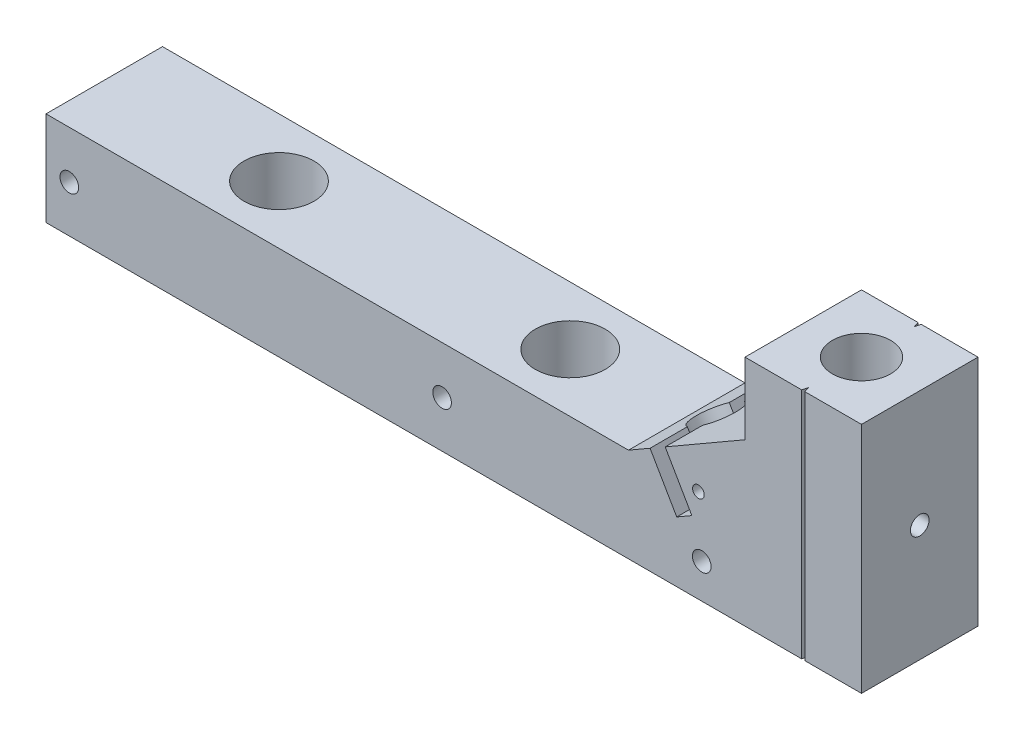
SolidWorks part; units mm, degrees
ref_plane "Front Plane" through (0, 0, 0) normal (0, 0, 1) x (1, 0, 0)
ref_plane "Top Plane" through (0, 0, 0) normal (0, 1, 0) x (1, 0, 0)
ref_plane "Right Plane" through (0, 0, 0) normal (1, 0, 0) x (0, 0, -1)
sketch "Sketch1" plane through (0, 0, 0) normal (0, 1, 0) x (1, 0, 0)
  line L1 (-13.6389, 9.0278) -> (6.3611, 9.0278)
  line L2 (-13.6389, 9.0278) -> (-13.6389, -0.9722)
  line L3 (-13.6389, -0.9722) -> (6.3611, -0.9722)
  line L4 (6.3611, 9.0278) -> (6.3611, -0.9722)
  dimension "D1" = 20
  dimension "D2" = 10
extrude "Boss-Extrude1" add sketch "Sketch1" along normal blind 20
sketch "Sketch2" plane through (0, 20, 0) normal (0, 1, 0) x (1, 0, 0)
  line L0 (-13.6389, 4.0278) -> (6.3611, 4.0278) construction
  line L1 (-13.6389, 9.0278) -> (-13.6389, -0.9722) construction
  line L2 (6.3611, -0.9722) -> (6.3611, 9.0278) construction
  line L3 (1.4951, -0.9722) -> (1.3611, -0.4722)
  line L4 (-13.6389, -0.9722) -> (6.3611, -0.9722) construction
  line L5 (1.3611, -0.4722) -> (1.2271, -0.9722)
  line L6 (1.4951, -0.9722) -> (1.2271, -0.9722)
  line L7 (1.3611, 8.5278) -> (1.2271, 9.0278)
  line L8 (1.4951, 9.0278) -> (1.3611, 8.5278)
  line L9 (1.4951, 9.0278) -> (1.2271, 9.0278)
  circle A0 centre (1.3611, 4.0278) radius 2.5
  dimension "D1" = 5
  dimension "D2" = 5
  dimension "D3" = 30
  dimension "D4" = 0.5
extrude "Cut-Extrude1" cut sketch "Sketch2" against normal through all
sketch "Sketch3" plane through (0, 0, 0.9722) normal (0, 0, 1) x (1, 0, 0)
  line L0 (-13.6389, 20) -> (-3.6389, 20)
  line L1 (-13.6389, 20) -> (1.2271, 20) construction
  line L2 (-3.6389, 13.8564) -> (-10.4894, 9.9013)
  line L3 (-13.6389, 20) -> (-13.6389, 0) construction
  line L4 (-13.6389, 8.0829) -> (-13.6389, 20)
  line L5 (-3.6389, 13.8564) -> (-3.6389, 20)
  line L6 (-13.6389, 0) -> (1.2271, 0) construction
  line L7 (-11.1389, 9.5263) -> (-5.6389, 0) construction
  line L8 (6.3611, 20) -> (6.3611, 0) construction
  line L10 (-10.4894, 9.9013) -> (-8.2009, 5.9375)
  line L11 (-11.7884, 9.1513) -> (-9.4999, 5.1875)
  line L12 (-8.2009, 5.9375) -> (-9.4999, 5.1875)
  line L13 (-11.7884, 9.1513) -> (-13.6389, 8.0829)
  point P1 (-8.8504, 5.5625)
  point P17 (-8.3889, 4.7631)
  dimension "D1" = 30
  dimension "D2" = 11
  dimension "D3" = 12
  dimension "D4" = 10
  dimension "D5" = 1.5
  dimension "D6" = 4.577
extrude "Cut-Extrude2" cut sketch "Sketch3" against normal through all
sketch "Sketch5" plane through (-6.9097, 11.968, 0) normal (-0.5, 0.866, 0) x (0.866, 0.5, 0)
  line L0 (-4.1334, 9.0278) -> (-4.1334, -0.9722) construction
  line L1 (-4.1334, 4.0278) -> (-5.6334, 4.0278) construction
  line L2 (-5.6334, 9.0278) -> (-5.6334, -0.9722) construction
  circle A0 centre (-4.8834, 4.0278) radius 1.95
  point P5 (-4.1334, 4.0278)
  dimension "D1" = 3.9
extrude "Cut-Extrude5" cut sketch "Sketch5" against normal through all
sketch "Sketch6" plane through (6.3611, 0, 0) normal (1, 0, 0) x (0, 0, -1)
  line L0 (9.0278, 20) -> (9.0278, 0) construction
  line L1 (-0.9722, 20) -> (9.0278, 20) construction
  point P0 (4.0278, 10)
  point P4 (9.0278, 10)
  point P8 (4.0278, 20)
hole_wizard "M2x0.4 Tapped Hole1" positions "Sketch7" profile "Sketch8" tap size "M2x0.4" standard "BSI"
sketch "Sketch7" plane through (6.3611, 0, 0) normal (1, 0, 0) x (0, 0, -1)
  point P0 (4.0278, 10)
sketch "Sketch8" plane through (6.3611, 10, -4.0278) normal (0, 1, 0) x (0, 0, -1)
  line L0 (0, 0) -> (0, 6.4807)
  line L1 (0, 6.4807) -> (0.8, 6)
  line L2 (0.8, 6) -> (0.8, 0)
  line L5 (0.8, 0) -> (0, 0)
  line L10 (0, 6.4807) -> (-0.8, 6) construction
  line L11 (0, -6.35) -> (0, 107.95) construction
  dimension "Tap Drill Dia." = 1.6
  dimension "Tap Drill Depth" = 6
  dimension "Drill Angle" = 118
cosmetic thread "Hole Thread1" parameters "D1"=4, "D2"=2
hole_wizard "M2x0.4 Tapped Hole2" positions "Sketch9" profile "Sketch10" tap size "M2x0.4" standard "BSI"
sketch "Sketch9" plane through (0, 0, 0.9722) normal (0, 0, 1) x (1, 0, 0)
  line L0 (-9.4999, 5.1875) -> (-8.2009, 5.9375) construction
  line L1 (-7.3504, 2.9644) -> (-8.8504, 5.5625) construction
  point P0 (-7.3504, 2.9644)
  dimension "D1" = 3
sketch "Sketch10" plane through (-7.3504, 2.9644, 0.9722) normal (1, 0, 0) x (0, -1, 0)
  line L0 (0, 0) -> (0, 6.4807)
  line L1 (0, 6.4807) -> (0.8, 6)
  line L2 (0.8, 6) -> (0.8, 0)
  line L5 (0.8, 0) -> (0, 0)
  line L10 (0, 6.4807) -> (-0.8, 6) construction
  line L11 (0, -6.35) -> (0, 107.95) construction
  dimension "Tap Drill Dia." = 1.6
  dimension "Tap Drill Depth" = 6
  dimension "Drill Angle" = 118
cosmetic thread "Hole Thread2" parameters "D1"=4, "D2"=2
sketch "Sketch14" plane through (-13.6389, 0, 0) normal (-1, 0, 0) x (0, 0, 1)
  line L4 (0.9722, 0) -> (0.9722, 8.0829)
  line L5 (0.9722, 8.0829) -> (-9.0278, 8.0829)
  line L6 (-9.0278, 8.0829) -> (-9.0278, 0)
  line L7 (-9.0278, 0) -> (0.9722, 0)
  line L8 (0.9722, 0) -> (0.9722, 8.0829)
  line L9 (0.9722, 8.0829) -> (-9.0278, 8.0829)
  line L10 (-9.0278, 8.0829) -> (-9.0278, 0)
  line L11 (-9.0278, 0) -> (0.9722, 0)
  dimension "D1" = 0
extrude "Boss-Extrude3" add sketch "Sketch14" along normal blind 50
sketch "Sketch15" plane through (0, 8.0829, 0) normal (0, 1, 0) x (1, 0, 0)
  line L1 (-63.6389, -0.9722) -> (-63.6389, 9.0278) construction
  line L2 (-13.6389, -0.9722) -> (-13.6389, 9.0278) construction
  circle A2 centre (-48.6389, 4.0278) radius 3
  circle A3 centre (-23.6389, 4.0278) radius 3
  point P8 (-63.6389, 4.0278)
  dimension "D1" = 6
  dimension "D2" = 6
  dimension "D4" = 10
  dimension "D3" = 25
extrude "Cut-Extrude7" cut sketch "Sketch15" against normal up to next
sketch "Sketch16" plane through (0, 0, 0.9722) normal (0, 0, 1) x (1, 0, 0)
  line L0 (-63.6389, 0) -> (1.2271, 0) construction
  line L3 (-13.6389, 0) -> (-13.6389, 8.0829) construction
  circle A0 centre (-61.6389, 4) radius 1
  circle A1 centre (-29.6389, 4) radius 1
  dimension "D1" = 2
  dimension "D2" = 2
  dimension "D5" = 16
  dimension "D4" = 32
  dimension "D3" = 4
sketch "Sketch18" plane through (0, 0, 0.9722) normal (0, 0, 1) x (1, 0, 0)
  line L0 (-63.6389, 0) -> (1.2271, 0) construction
  line L1 (-13.6389, 0) -> (-13.6389, 8.0829) construction
  circle A0 centre (-7.6389, 8) radius 0.5
  dimension "D1" = 1
  dimension "D2" = 8
  dimension "D3" = 6
extrude "Cut-Extrude9" cut sketch "Sketch18" against normal blind 3
hole_wizard "M2x0.4 Tapped Hole3" positions "Sketch21" profile "Sketch22" tap size "M2x0.4" standard "BSI" end condition through all
sketch "Sketch21" plane through (0, 0, 0.9722) normal (0, 0, 1) x (1, 0, 0)
  point P0 (-61.6389, 4)
  point P4 (-29.6389, 4)
sketch "Sketch22" plane through (-61.6389, 4, 0.9722) normal (1, 0, 0) x (0, -1, 0)
  line L0 (0, 0) -> (0, 10)
  line L1 (0, 10) -> (0.8, 10)
  line L2 (0.8, 10) -> (0.8, 0)
  line L5 (0.8, 0) -> (0, 0)
  line L11 (0, -6.35) -> (0, 107.95) construction
  dimension "Thru Tap Drill Dia." = 1.6
  dimension "Thru Tap Drill Depth" = 10
cosmetic thread "Hole Thread3" parameters "D2"=2
cosmetic thread "Hole Thread4" parameters "D2"=2
